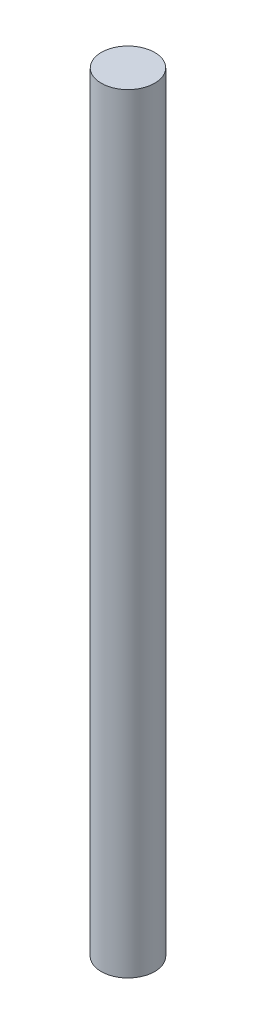
SolidWorks part; units mm, degrees
ref_plane "Front" through (0, 0, 0) normal (0, 0, 1) x (1, 0, 0)
ref_plane "Top" through (0, 0, 0) normal (0, 1, 0) x (1, 0, 0)
ref_plane "Right" through (0, 0, 0) normal (1, 0, 0) x (0, 0, -1)
sketch "Sketch1" plane through (0, 0, 0) normal (0, 1, 0) x (1, 0, 0)
  circle A0 centre (0, 0) radius 1.5875
  dimension "D1" = 3.175
extrude "Boss-Extrude1" add sketch "Sketch1" along normal blind 45.72
